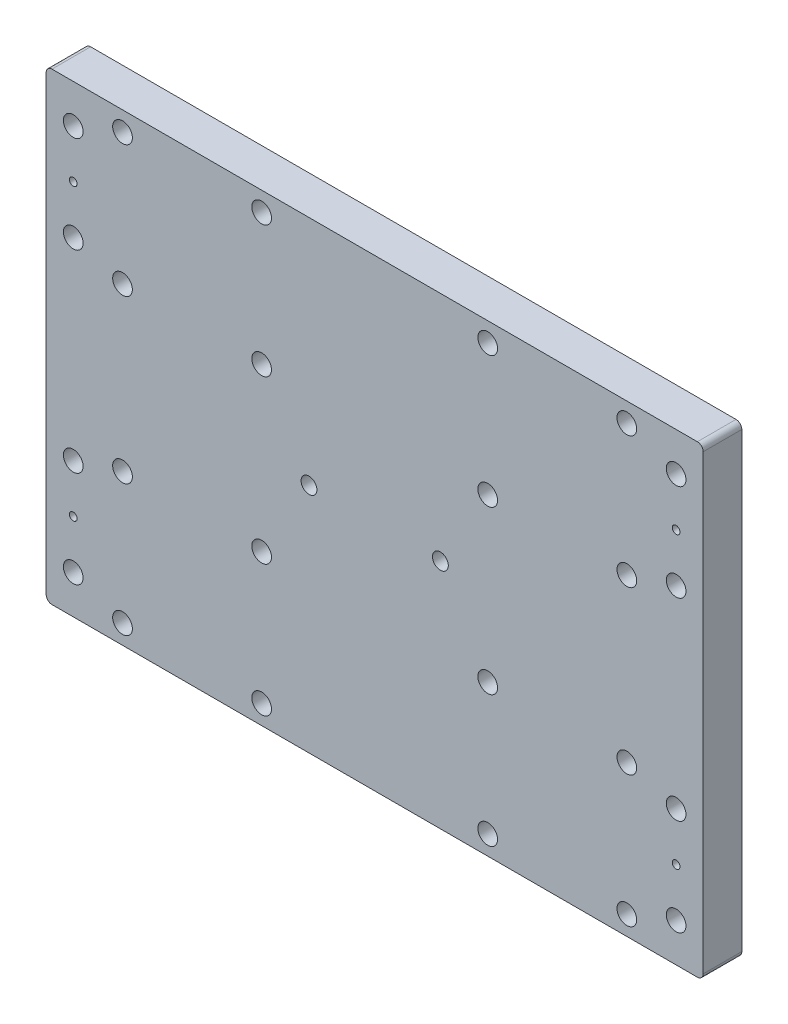
SolidWorks part; units mm, degrees
ref_plane "Front Plane" through (0, 0, 0) normal (0, 0, 1) x (1, 0, 0)
ref_plane "Top Plane" through (0, 0, 0) normal (0, 1, 0) x (1, 0, 0)
ref_plane "Right Plane" through (0, 0, 0) normal (1, 0, 0) x (0, 0, -1)
sketch "Sketch1" plane through (0, 0, 0) normal (0, 0, 1) x (1, 0, 0)
  line L1 (85, -60) -> (-85, -60)
  line L2 (85, -60) -> (85, 60)
  line L3 (85, 60) -> (-85, 60)
  line L4 (-85, -60) -> (-85, 60)
  line L5 (85, -60) -> (-85, 60) construction
  line L6 (85, 60) -> (-85, -60) construction
  point P0 (0, 0)
  dimension "D1" = 170
  dimension "D2" = 120
extrude "Boss-Extrude1" add sketch "Sketch1" along normal mid plane 10
sketch "Sketch2" plane through (0, 0, 5) normal (0, 0, 1) x (1, 0, 0)
  line L0 (-65.25, 71) -> (-65.25, -71) construction
  line L1 (65.25, -71) -> (65.25, 71) construction
  line L2 (-29.25, 71) -> (-29.25, -71) construction
  line L3 (29.25, -71) -> (29.25, 71) construction
  line L4 (70.6711, 55) -> (-71.3289, 55) construction
  line L5 (-71.3289, -55) -> (70.6711, -55) construction
  line L6 (70.6711, 21) -> (-71.3289, 21) construction
  line L7 (-71.3289, -21) -> (70.6711, -21) construction
  line L8 (85, 60) -> (-85, 60) construction
  line L9 (-85, -60) -> (85, -60) construction
  line L10 (-85, 60) -> (-85, -60) construction
  line L11 (85, -60) -> (85, 60) construction
  circle A0 centre (-65.25, 55) radius 2.55
  circle A1 centre (-29.25, 55) radius 2.55
  circle A2 centre (-29.25, 21) radius 2.55
  circle A3 centre (-65.25, 21) radius 2.55
  circle A4 centre (65.25, 55) radius 2.55
  circle A5 centre (65.25, 21) radius 2.55
  circle A6 centre (29.25, 21) radius 2.55
  circle A7 centre (29.25, 55) radius 2.55
  circle A8 centre (-65.25, -21) radius 2.55
  circle A9 centre (-29.25, -21) radius 2.55
  circle A10 centre (-29.25, -55) radius 2.55
  circle A11 centre (-65.25, -55) radius 2.55
  circle A12 centre (29.25, -21) radius 2.55
  circle A13 centre (65.25, -21) radius 2.55
  circle A14 centre (65.25, -55) radius 2.55
  circle A15 centre (29.25, -55) radius 2.55
  dimension "D1" = 5.1
  dimension "D2" = 5.1
  dimension "D3" = 5.1
  dimension "D4" = 5.1
  dimension "D5" = 5.1
  dimension "D6" = 5.1
  dimension "D7" = 5.1
  dimension "D8" = 5.1
  dimension "D9" = 5.1
  dimension "D10" = 5.1
  dimension "D11" = 5.1
  dimension "D12" = 5.1
  dimension "D13" = 5.1
  dimension "D14" = 5.1
  dimension "D15" = 5.1
  dimension "D16" = 5.1
  dimension "D17" = 5
  dimension "D18" = 5
  dimension "D19" = 34
  dimension "D20" = 34
  dimension "D21" = 36
  dimension "D22" = 36
  dimension "D23" = 19.75
  dimension "D24" = 19.75
extrude "Cut-Extrude1" cut sketch "Sketch2" against normal through all
sketch "Sketch4" plane through (0, 0, 5) normal (0, 0, 1) x (1, 0, 0)
  line L3 (-17, 0) -> (17, 0) construction
  circle A0 centre (-17, 0) radius 2.05
  circle A3 centre (17, 0) radius 2.05
  point P0 (0, 0)
  dimension "D3" = 4.1
  dimension "D4" = 4.1
  dimension "D1" = 34
extrude "Cut-Extrude3" cut sketch "Sketch4" against normal through all
fillet "Fillet1" radius 1.5 4 edges at (-85, -60, 0) (85, -60, 0) (85, 60, 0) (-85, 60, 0)
sketch "Sketch6" plane through (0, 0, 5) normal (0, 0, 1) x (1, 0, 0)
  line L0 (-78, -1002.1032) -> (-78, 48997.8968) construction
  line L1 (78, -1010.3548) -> (78, 48989.6452) construction
  line L2 (-85, 58.5) -> (-85, -58.5) construction
  line L3 (85, -58.5) -> (85, 58.5) construction
  line L4 (83.5, 60) -> (-83.5, 60) construction
  line L5 (-83.5, -60) -> (83.5, -60) construction
  circle A0 centre (-78, 50) radius 2.55
  circle A1 centre (-78, 37.5) radius 1
  circle A2 centre (-78, 25) radius 2.55
  circle A3 centre (-78, -25) radius 2.55
  circle A4 centre (-78, -37.5) radius 1
  circle A5 centre (-78, -50) radius 2.55
  dimension "D3" = 5.1
  dimension "D4" = 2
  dimension "D5" = 5.1
  dimension "D6" = 5.1
  dimension "D7" = 5.1
  dimension "D8" = 2
  dimension "D9" = 10
  dimension "D12" = 35
  dimension "D14" = 10
  dimension "D1" = 7
  dimension "D2" = 7
  dimension "D10" = 22.5
  dimension "D11" = 35
  dimension "D13" = 22.5
extrude "Cut-Extrude5" cut sketch "Sketch6" against normal through all
mirror "Mirror1" about plane through (0, 0, 0) normal (1, 0, 0) of "Cut-Extrude5"
equation "\"D23@Sketch2\"=5.75+14"
equation "\"D24@Sketch2\"=5.75+14"
equation "\"D4@Sketch4\"=\"D3@Sketch4\""
equation "\"D5@Sketch6\" = \"D3@Sketch6\""
equation "\"D6@Sketch6\" = \"D3@Sketch6\""
equation "\"D7@Sketch6\"=\"D3@Sketch6\""
equation "\"D22@Sketch2\"=\"D21@Sketch2\""
equation "\"D20@Sketch2\"=\"D19@Sketch2\""
